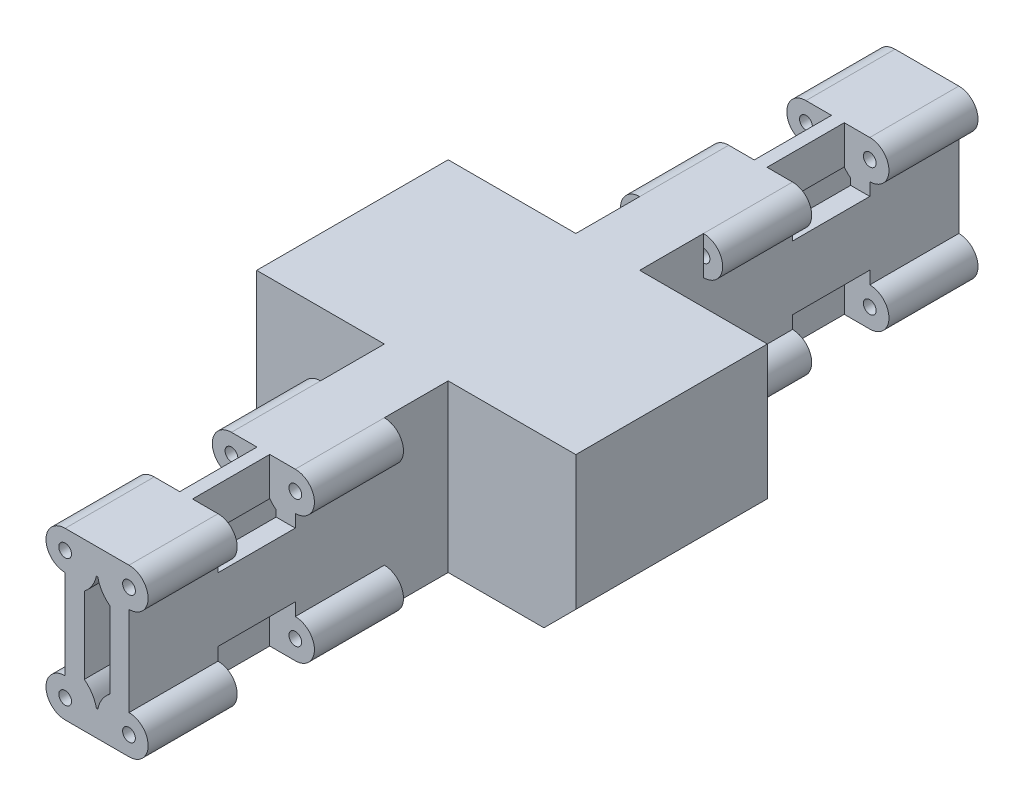
SolidWorks part; units mm, degrees
material "ABS"
ref_plane "Спереди" through (0, 0, 0) normal (0, 0, 1) x (1, 0, 0)
ref_plane "Сверху" through (0, 0, 0) normal (0, 1, 0) x (1, 0, 0)
ref_plane "Справа" through (0, 0, 0) normal (1, 0, 0) x (0, 0, -1)
sketch "Эскиз1" plane through (0, 0, 0) normal (0, 0, 1) x (1, 0, 0)
  line L0 (0, 30.7154) -> (0, -31.2898) construction
  line L2 (25, -13.2872) -> (-25, -13.2872)
  line L3 (25, -13.2872) -> (25, 12.7128)
  line L4 (25, 12.7128) -> (-25, 12.7128)
  line L5 (-25, -13.2872) -> (-25, 12.7128)
  line L6 (25, -13.2872) -> (-25, 12.7128) construction
  line L7 (25, 12.7128) -> (-25, -13.2872) construction
  point P3 (0, -0.2872)
  dimension "D1" = 50
  dimension "D2" = 26
extrude "Бобышка-Вытянуть1" add sketch "Эскиз1" along normal mid plane 130
sketch "Эскиз7" plane through (0, 0, 65) normal (0, 0, 1) x (1, 0, 0)
  line L0 (0, 12.7128) -> (0, -13.2872) construction
  line L1 (-25, -13.2872) -> (-5, -13.2872)
  line L2 (-25, -13.2872) -> (-25, 12.7128)
  line L3 (-25, 12.7128) -> (-5, 12.7128)
  line L4 (-5, -13.2872) -> (-5, 12.7128)
  line L5 (25, 12.7128) -> (-25, 12.7128) construction
  line L6 (-25, -13.2872) -> (25, -13.2872) construction
  dimension "D1" = 26
  dimension "D2" = 5
extrude "Вырез-Вытянуть5" cut sketch "Эскиз7" against normal blind 50
sketch "Эскиз4" plane through (0, 0, 65) normal (0, 0, 1) x (1, 0, 0)
  line L1 (-5, -13.2872) -> (-5, 12.7128) construction
  line L2 (-25, -13.2872) -> (-5, -13.2872) construction
  circle A0 centre (-5, 9.7128) radius 3
  circle A1 centre (-5, -10.2872) radius 3
  line M8 (-5, 12.7128) -> (-5, -13.2872)
  dimension "D1" = 6
  dimension "D2" = 20
  dimension "D3" = 3
extrude "Бобышка-Вытянуть3" add sketch "Эскиз4" against normal blind 40 contours A1 M8 | A1 M8 | A0 | A0 region at (-3.7268, 9.7128, 65) region at (-3.7268, -10.2872, 65) region at (-6.2732, -10.2872, 65)
sketch "Эскиз5" plane through (-5, 0, 0) normal (-1, 0, 0) x (0, 0, 1)
  line L5 (25, -13.2872) -> (65, -13.2872) construction
  line L6 (38.95, -13.2872) -> (51.05, -13.2872)
  line L11 (38.95, -13.2872) -> (38.95, -5.2872)
  line L12 (38.95, -5.2872) -> (51.05, -5.2872)
  line L13 (51.05, -13.2872) -> (51.05, -5.2872)
  line L19 (65, 6.7128) -> (65, 12.7128) construction
  line L29 (38.95, 4.7128) -> (51.05, 4.7128)
  line L30 (38.95, 4.7128) -> (38.95, 12.7128)
  line L31 (38.95, 12.7128) -> (51.05, 12.7128)
  line L32 (51.05, 4.7128) -> (51.05, 12.7128)
  line L33 (25, 12.7128) -> (65, 12.7128) construction
  dimension "D1" = 12.1
  dimension "D2" = 8
  dimension "D4" = 8
  dimension "D3" = 13.95
extrude "Вырез-Вытянуть3" cut sketch "Эскиз5" against normal mid plane 8
sketch "Эскиз6" plane through (0, 0, 65) normal (0, 0, 1) x (1, 0, 0)
  circle A0 centre (-5, 9.7128) radius 1
  circle A1 centre (-5, -10.2872) radius 1
  dimension "D1" = 2
extrude "Вырез-Вытянуть4" cut sketch "Эскиз6" against normal blind 40
mirror "Зеркальное отражение1" about plane through (0, 0, 0) normal (0, 0, 1) of "Вырез-Вытянуть5", "Вырез-Вытянуть4", "Вырез-Вытянуть3", "Бобышка-Вытянуть3"
mirror "Зеркальное отражение2" about plane through (0, 0, 0) normal (1, 0, 0) of "Зеркальное отражение1"
sketch "Эскиз9" plane through (0, 0, 0) normal (0, 0, 1) x (1, 0, 0)
  line L0 (0, 14.7189) -> (0, -15.9167) construction
  line L1 (-5, 10.7128) -> (-5, 8.7128) construction
  line L2 (5, 10.7128) -> (5, 8.7128) construction
  line L3 (-5, -9.2872) -> (-5, -11.2872) construction
  line L4 (5, -9.2872) -> (5, -11.2872) construction
  line L5 (-2, 5.7128) -> (-2, -6.2872)
  line L6 (-0.101, -9.2872) -> (0.101, -9.2872)
  line L7 (2, -6.2872) -> (2, 5.7128)
  line L8 (-0.101, 8.7128) -> (0.101, 8.7128)
  line L9 (5, 12.7128) -> (-5, 12.7128) construction
  line L10 (-5, -7.2872) -> (-5, 6.7128) construction
  line L11 (-5, -13.2872) -> (5, -13.2872) construction
  circle A0 centre (-5, 9.7128) radius 5
  circle A1 centre (5, 9.7128) radius 5
  circle A2 centre (-5, -10.2872) radius 5
  circle A3 centre (5, -10.2872) radius 5
  dimension "D1" = 10
  dimension "D2" = 4
  dimension "D3" = 3
  dimension "D4" = 4
extrude "Вырез-Вытянуть7" cut sketch "Эскиз9" against normal through all both and the other way through all contours L0 L8 A0 L5 A2 L6 | L8 L0 L6 A3 L7 A1 region at (0.9305, -0.2872, 0) region at (-0.9305, -0.2872, 0)
sketch "Эскиз10" plane through (0, 0, 15) normal (0, 0, 1) x (1, 0, 0)
  line L0 (25, 12.7128) -> (25, -13.2872) construction
  line L2 (-5, -13.2872) -> (5, -13.2872) construction
  line L4 (-25, 12.7128) -> (-25, -13.2872) construction
  line L5 (25, 12.7128) -> (25, -8.2872)
  line L6 (-25, -8.2872) -> (-20, -13.2872)
  line L7 (-20, -13.2872) -> (20, -13.2872)
  line L8 (25, -8.2872) -> (20, -13.2872)
  line L9 (-25, 12.7128) -> (-25, -8.2872)
  line L10 (-25, -8.2872) -> (-25, -13.2872)
  line L11 (-25, -13.2872) -> (-20, -13.2872)
  line L12 (20, -13.2872) -> (25, -13.2872)
  line L13 (25, -13.2872) -> (25, -8.2872)
  line M4 (-25, 12.7128) -> (-25, -13.2872)
  line M5 (-25, -13.2872) -> (-5, -13.2872)
extrude "Вырез-Вытянуть8" cut sketch "Эскиз10" against normal up to next contours L6 M4 M5 | L12 L13 L8 region at (23.3333, -11.6205, 15) region at (-23.3333, -11.6205, 15)
equation "\"D4@Эскиз5\"=\"D2@Эскиз5\""
equation "\"D4@Эскиз9\"=\"D2@Эскиз9\""
